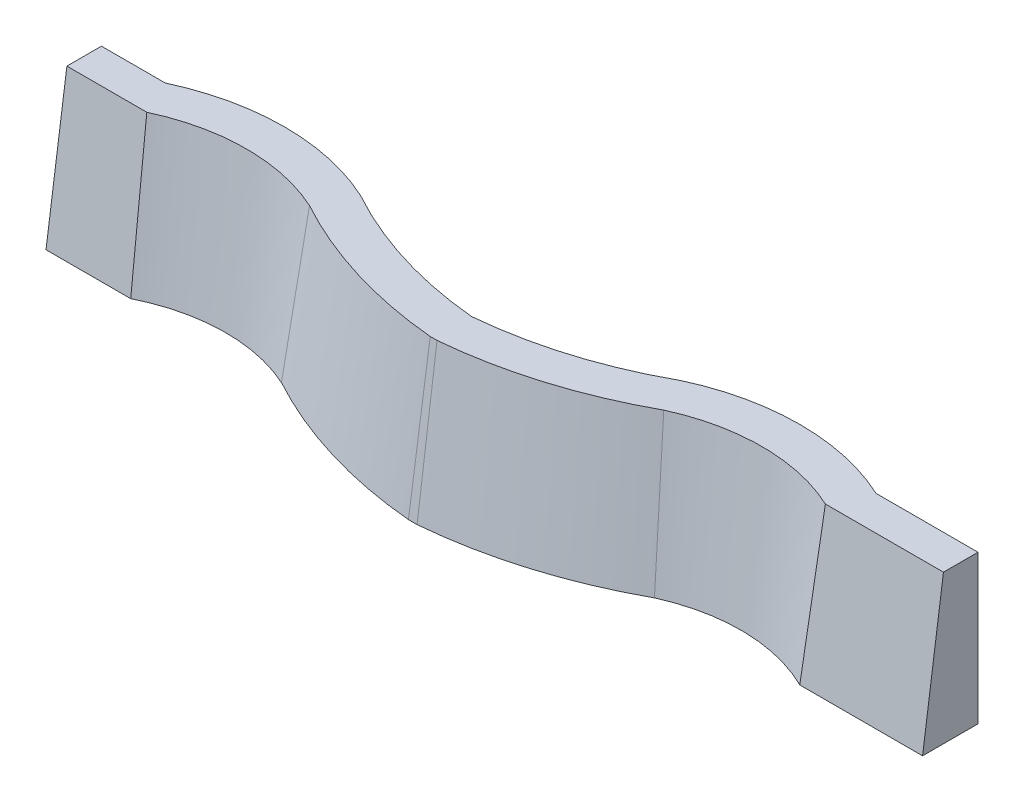
SolidWorks part; units mm, degrees
ref_plane "Front Plane" through (0, 0, 0) normal (0, 0, 1) x (1, 0, 0)
ref_plane "Top Plane" through (0, 0, 0) normal (0, 1, 0) x (1, 0, 0)
ref_plane "Right Plane" through (0, 0, 0) normal (1, 0, 0) x (0, 0, -1)
sketch "Sketch1" plane through (0, 0, 0) normal (0, 1, 0) x (1, 0, 0)
  line L0 (-110, -30) -> (-110, -41.2422) construction
  line L1 (-39.8399, -30) -> (34.8399, -30) construction
  line L2 (110, -30) -> (110, -41.2422) construction
  line L3 (0, -142.6423) -> (0, 36.4059) construction
  line L4 (0, -100) -> (0, 70) construction
  line L5 (-42.9151, -50) -> (42.9151, -50) construction
  line L6 (-110, -41.2422) -> (-39.8399, -43.9889) construction
  line L7 (39.8399, -43.9889) -> (110, -41.2422) construction
  line L8 (-110, -30) -> (-39.8399, -30) construction
  line L9 (110, -30) -> (34.8399, -30) construction
  line L10 (-39.8399, -30) -> (-39.8399, -43.9889) construction
  line L11 (34.8399, -30) -> (39.8399, -43.9889) construction
  arc A0 (-39.8399, -30) -> (34.8399, -30) centre (-2.5, 38.0274) ccw construction
  arc A1 (-39.8399, -43.9889) -> (0, -50) centre (-1.9011, 72.4289) ccw construction
  arc A2 (39.8399, -43.9889) -> (0, -50) centre (1.9011, 72.4289) cw construction
  dimension "D1" = 77.6015
  dimension "D2" = 122.4436
  dimension "D3" = 34.8399
  dimension "D4" = 70.1601
  dimension "D5" = 70.1601
  dimension "D6" = 92.242
  dimension "D7" = 13.9889
ref_plane "Bottom Of Chassis" through (0, -15, 0) normal (0, 1, 0) x (1, 0, 0)
ref_plane "Top of Chassis" through (0, 24, 0) normal (0, 1, 0) x (1, 0, 0)
sketch "Sketch3" plane through (0, 24, 0) normal (0, 1, 0) x (1, 0, 0)
  line L6 (-0.8962, -52.8359) -> (0.8962, -52.8359)
  line L7 (-110, -30) -> (-110, -39.0641)
  line L12 (-110, -39.0641) -> (-89.0261, -39.0641)
  line L13 (-110, -30) -> (-93.25, -30)
  line L16 (89.0261, -39.0641) -> (120, -39.0641) construction
  line L17 (89.0261, -39.0641) -> (120, -39.0641)
  line L18 (120, -30) -> (120, -39.0641) construction
  line L19 (120, -30) -> (120, -39.0641)
  line L20 (93.25, -30) -> (120, -30)
  arc A8 (-46.4813, -38.9279) -> (-89.0261, -39.0641) centre (-67.6063, -85.0296) ccw construction
  arc A9 (-93.25, -30) -> (-41.9625, -30) centre (-67.6063, -85.0296) cw
  arc A13 (-41.9625, -30) -> (-93.25, -30) centre (-67.6063, -85.0296) ccw construction
  arc A14 (-89.0261, -39.0641) -> (-46.4813, -38.9279) centre (-67.6063, -85.0296) cw
  arc A15 (-46.4813, -38.9279) -> (-0.8962, -52.8359) centre (9.5248, 62.9793) ccw
  arc A20 (-46.4813, -38.9279) -> (-0.8962, -52.8359) centre (9.5248, 62.9793) ccw construction
  arc A21 (-41.9625, -30) -> (0, -42.8761) centre (9.5248, 62.9793) ccw
  arc A22 (-41.9625, -30) -> (0, -42.8761) centre (9.5248, 62.9793) ccw construction
  arc A23 (0.8962, -52.8359) -> (46.4813, -38.9279) centre (-9.5248, 62.9793) ccw
  arc A24 (0.8962, -52.8359) -> (46.4813, -38.9279) centre (-9.5248, 62.9793) ccw construction
  arc A25 (0, -42.8761) -> (41.9625, -30) centre (-9.5248, 62.9793) ccw
  arc A26 (0, -42.8761) -> (41.9625, -30) centre (-9.5248, 62.9793) ccw construction
  arc A27 (93.25, -30) -> (41.9625, -30) centre (67.6063, -85.0296) ccw construction
  arc A28 (93.25, -30) -> (41.9625, -30) centre (67.6063, -85.0296) ccw
  arc A29 (89.0261, -39.0641) -> (46.4813, -38.9279) centre (67.6063, -85.0296) ccw construction
  arc A30 (89.0261, -39.0641) -> (46.4813, -38.9279) centre (67.6063, -85.0296) ccw
  point P19 (-27.3251, -36.417)
  point P20 (-73.6989, -83.1159)
  point P21 (0, -17.3273)
  point P27 (-70.2175, -80.192)
  point P44 (-112.1058, -33.2855)
extrude "Boss-Extrude1" add sketch "Sketch3" against normal up to surface (39 mm away) contours A30 L17 L19 L20 A28 A25 A21 A9 L13 L7 L12 A14 A15 A23 region at (-23.7326, 24, 46.0256) up to plane "Bottom Of Chassis"
draft "Draft2" type of draft neutral plane draft angle 8 faces to draft 7 face at (0, 4.5, 52.8359) face at (104.5131, 4.5, 39.0641) face at (67.7612, 4.5, 36.6573) face at (24.0488, 4.5, 47.0621) face at (-24.0488, 4.5, 47.0621) face at (-67.7612, 4.5, 36.6573) face at (-99.5131, 4.5, 39.0641) neutral plane through (0, 24, 0) neutral plane normal (0, 1, 0) parameters "D1"=8
